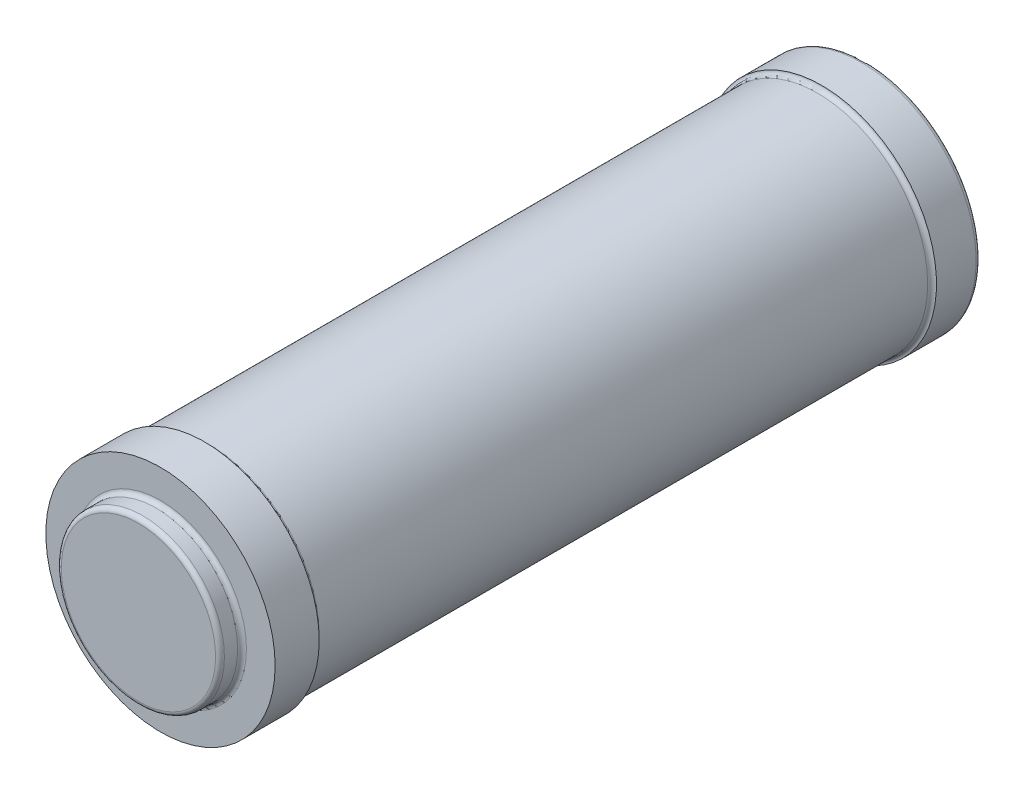
SolidWorks part; units mm, degrees
material "PVC Rígido"
ref_plane "Plano frontal" through (0, 0, 0) normal (0, 0, 1) x (1, 0, 0)
ref_plane "Plano superior" through (0, 0, 0) normal (0, 1, 0) x (1, 0, 0)
ref_plane "Plano direito" through (0, 0, 0) normal (1, 0, 0) x (0, 0, -1)
sketch "Esboço1" plane through (0, 0, 0) normal (0, 0, 1) x (1, 0, 0)
  circle A0 centre (-12.7458, -1.5379) radius 5
extrude "Ressalto-extrusão1" add sketch "Esboço1" along normal blind 30
sketch "Esboço2" plane through (0, 0, 30) normal (0, 0, 1) x (1, 0, 0)
  circle A0 centre (-12.7458, -1.5379) radius 4.8
extrude "Corte-extrusão1" cut sketch "Esboço2" against normal blind 30
sketch "Esboço3" plane through (0, 0, 30) normal (0, 0, 1) x (1, 0, 0)
  circle A2 centre (-12.7458, -1.5379) radius 5.2
  circle A3 centre (-12.7458, -1.5379) radius 5.2
  dimension "D1" = 0.2
extrude "Ressalto-extrusão2" add sketch "Esboço3" along normal blind 1 and the other way blind 1
sketch "Esboço4" plane through (0, 0, 31) normal (0, 0, 1) x (1, 0, 0)
  circle A2 centre (-12.7458, -1.5379) radius 3.7
  circle A3 centre (-12.7458, -1.5379) radius 3.7
  dimension "D1" = 1.5
extrude "Ressalto-extrusão3" add sketch "Esboço4" along normal blind 1
sketch "Esboço7" plane through (0, 0, 0) normal (0, 0, -1) x (-1, 0, 0)
  circle A2 centre (12.7458, -1.5379) radius 5.2
  circle A3 centre (12.7458, -1.5379) radius 5.2
  dimension "D1" = 0.2
extrude "Ressalto-extrusão6" add sketch "Esboço7" along normal blind 1 and the other way blind 1
fillet "Filete1" radius 0.2 5 edges at (-9.0458, -1.5379, 32) (-9.0458, -1.5379, 31) (-17.9458, -1.5379, -1) (-17.7458, -1.5379, 1) (-7.7458, -1.5379, 29)
